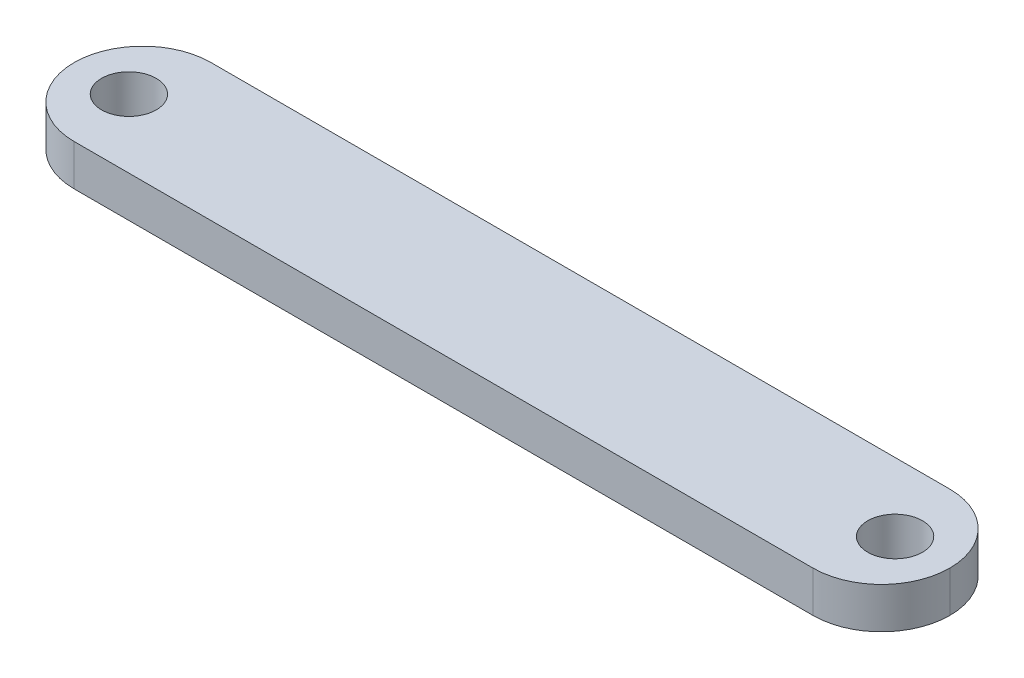
SolidWorks part; units mm, degrees
material "6061-T6 (SS)"
ref_plane "Front Plane" through (0, 0, 0) normal (0, 0, 1) x (1, 0, 0)
ref_plane "Top Plane" through (0, 0, 0) normal (0, 1, 0) x (1, 0, 0)
ref_plane "Right Plane" through (0, 0, 0) normal (1, 0, 0) x (0, 0, -1)
sketch "Sketch1" plane through (0, 0, 0) normal (0, 1, 0) x (1, 0, 0)
  line L0 (0, 15.875) -> (203.2, 15.875) construction
  line L1 (0, 0) -> (203.2, 0)
  line L2 (0, 0) -> (0, 31.75)
  line L3 (0, 31.75) -> (203.2, 31.75)
  line L4 (203.2, 0) -> (203.2, 31.75)
  circle A0 centre (12.7, 15.875) radius 6.35
  circle A1 centre (190.5, 15.875) radius 6.35
  point P11 (101.6, 15.875)
  dimension "D5" = 12.7
  dimension "D1" = 31.75
  dimension "D2" = 203.2
  dimension "D3" = 88.9
  dimension "D4" = 88.9
extrude "Boss-Extrude1" add sketch "Sketch1" along normal blind 9.525
fillet "Fillet1" radius 15.875 4 edges at (203.2, 4.7625, -31.75) (203.2, 4.7625, 0) (0, 4.7625, -31.75) (0, 4.7625, 0)
